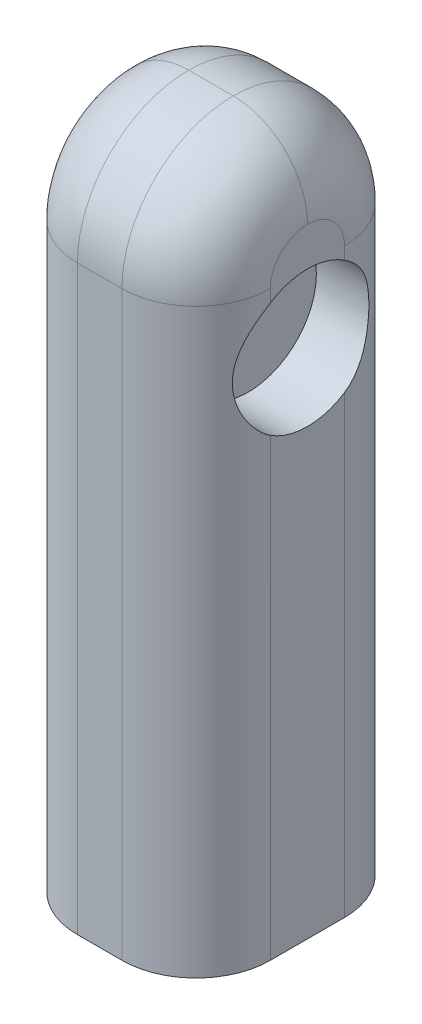
SolidWorks part; units mm, degrees
ref_plane "Front Plane" through (0, 0, 0) normal (0, 0, 1) x (1, 0, 0)
ref_plane "Top Plane" through (0, 0, 0) normal (0, 1, 0) x (1, 0, 0)
ref_plane "Right Plane" through (0, 0, 0) normal (1, 0, 0) x (0, 0, -1)
sketch "Sketch2" plane through (0, 0, 0) normal (0, 1, 0) x (1, 0, 0)
  line L1 (-13, 15) -> (13, 15)
  line L2 (-13, 15) -> (-13, -15)
  line L3 (-13, -15) -> (13, -15)
  line L4 (13, 15) -> (13, -15)
  line L5 (-13, 15) -> (13, -15) construction
  line L6 (-13, -15) -> (13, 15) construction
  point P0 (0, 0)
  dimension "D1" = 30
  dimension "D2" = 26
extrude "Boss-Extrude1" add sketch "Sketch2" along normal blind 93.4
sketch "Sketch3" plane through (13, 0, 0) normal (1, 0, 0) x (0, 0, -1)
  line L0 (-15, 93.4) -> (15, 93.4) construction
  circle A0 centre (0, 69) radius 9.2
  dimension "D1" = 18.4
  dimension "D2" = 24.4
extrude "Cut-Extrude1" cut sketch "Sketch3" against normal blind 8
sketch "Sketch4" plane through (-13, 0, 0) normal (-1, 0, 0) x (0, 0, 1)
  line L1 (-15, 93.4) -> (15, 93.4) construction
  circle A0 centre (0, 69) radius 9.2
  dimension "D1" = 18.4
  dimension "D2" = 24.4
extrude "Cut-Extrude2" cut sketch "Sketch4" against normal blind 8 contours A0
fillet "Fillet1" radius 15 2 edges at (0, 93.4, 15) (0, 93.4, -15)
sketch "Sketch9" plane through (0, 0, 0) normal (0, -1, 0) x (1, 0, 0)
  line L0 (13, -15) -> (-13, -15) construction
  line L1 (-7.5, 15) -> (7.5, 15)
  line L2 (-7.5, 15) -> (-7.5, -15)
  line L3 (-7.5, -15) -> (7.5, -15)
  line L4 (7.5, 15) -> (7.5, -15)
  line L5 (-7.5, 15) -> (7.5, -15) construction
  line L6 (-7.5, -15) -> (7.5, 15) construction
  point P0 (0, 0)
  dimension "D1" = 15
fillet "Fillet4" radius 10 4 edges at (-13, 39.2, 15) (-13, 89.0066, 10.6066) (-13, 89.0066, -10.6066) (-13, 39.2, -15)
fillet "Fillet5" radius 10 4 edges at (13, 39.2, -15) (13, 89.0066, -10.6066) (13, 89.0066, 10.6066) (13, 39.2, 15)
